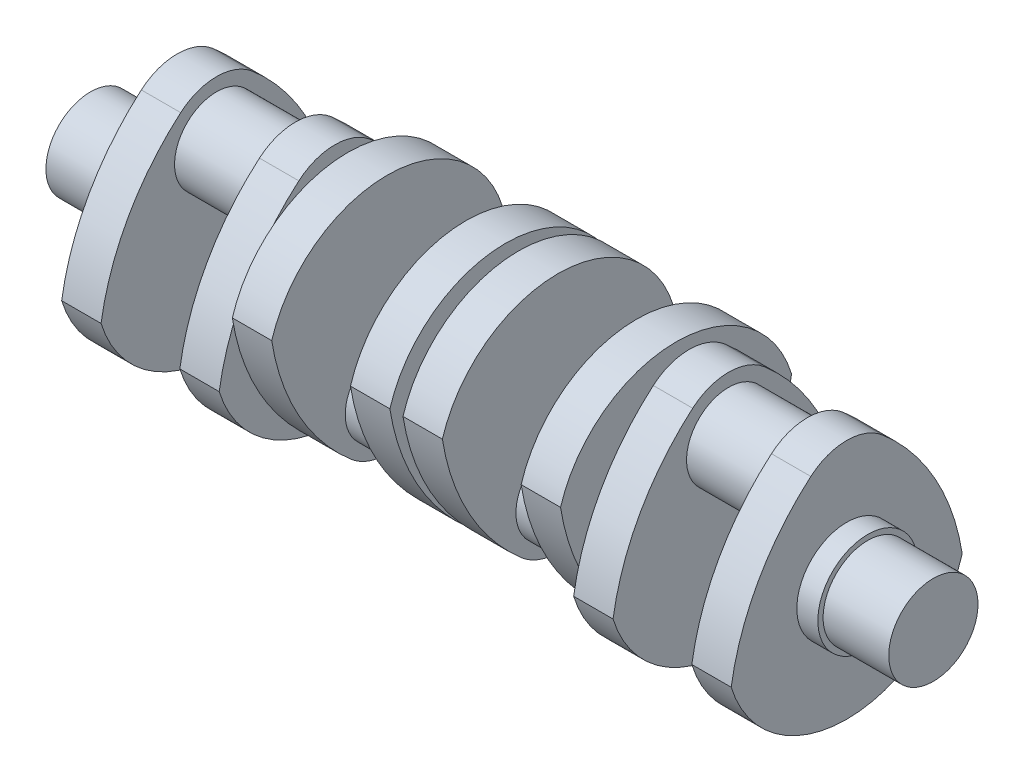
SolidWorks part; units mm, degrees
ref_plane "Front Plane" through (0, 0, 0) normal (0, 0, 1) x (1, 0, 0)
ref_plane "Top Plane" through (0, 0, 0) normal (0, 1, 0) x (1, 0, 0)
ref_plane "Right Plane" through (0, 0, 0) normal (1, 0, 0) x (0, 0, -1)
sketch "Sketch2" plane through (0, 0, 0) normal (1, 0, 0) x (0, 0, -1)
  circle A0 centre (0, 0) radius 17
  circle A1 centre (0, 0) radius 19
  dimension "D1" = 38
  dimension "D2" = 34
extrude "Boss-Extrude1" add sketch "Sketch2" against normal blind 25 contours A0
extrude "Boss-Extrude2" add sketch "Sketch2<4>" along normal blind 8 contours A1
sketch "Sketch2<4>" plane through (0, 0, 0) normal (1, 0, 0) x (0, 0, -1) same geometry as "Sketch2"
sketch "Sketch4" plane through (8, 0, 0) normal (1, 0, 0) x (0, 0, -1)
  arc A0 (-13.6681, 40.9431) -> (13.6681, 40.9431) centre (0, 25) cw
  arc A1 (-44, -13.4164) -> (44, -13.4164) centre (0, 0) ccw
  arc A2 (-13.6681, 40.9431) -> (-44, -13.4164) centre (44.9095, -27.3845) ccw
  arc A3 (13.6681, 40.9431) -> (44, -13.4164) centre (-44.9095, -27.3845) cw
  dimension "D3" = 46
  dimension "D4" = 21
  dimension "D5" = 90
  dimension "D6" = 90
  dimension "D1" = 25
  dimension "D2" = 88
extrude "Boss-Extrude3" add sketch "Sketch4" along normal blind 15
sketch "Sketch5" plane through (23, 0, 0) normal (1, 0, 0) x (0, 0, -1)
  circle A0 centre (0, 25) radius 16
  dimension "D1" = 32
extrude "Boss-Extrude4" add sketch "Sketch5" along normal blind 15
mirror "Mirror1" about plane through (38, 25, 0) normal (1, 0, 0) of "Boss-Extrude4", "Boss-Extrude3"
sketch "Sketch6" plane through (68, 0, 0) normal (1, 0, 0) x (0, 0, -1)
  circle A0 centre (0, 0) radius 17
  dimension "D1" = 34
extrude "Boss-Extrude5" add sketch "Sketch6" along normal blind 5
sketch "Sketch7" plane through (73, 0, 0) normal (1, 0, 0) x (0, 0, -1)
  arc A8 (-13.6681, -40.9431) -> (13.6681, -40.9431) centre (0, -25) ccw
  arc A9 (-44, 13.4164) -> (-13.6681, -40.9431) centre (44.9095, 27.3845) ccw
  arc A10 (44, 13.4164) -> (-44, 13.4164) centre (0, 0) ccw
  arc A11 (13.6681, -40.9431) -> (44, 13.4164) centre (-44.9095, 27.3845) ccw
extrude "Boss-Extrude6" add sketch "Sketch7" along normal blind 15
sketch "Sketch8" plane through (88, 0, 0) normal (1, 0, 0) x (0, 0, -1)
  circle A0 centre (0, -25) radius 16
  dimension "D1" = 32
  dimension "D2" = 25
extrude "Boss-Extrude7" add sketch "Sketch8" along normal blind 30
sketch "Sketch9" plane through (118, 0, 0) normal (1, 0, 0) x (0, 0, -1)
  arc A4 (-13.6681, -40.9431) -> (13.6681, -40.9431) centre (0, -25) ccw
  arc A5 (13.6681, -40.9431) -> (44, 13.4164) centre (-44.9095, 27.3845) ccw
  arc A6 (44, 13.4164) -> (-44, 13.4164) centre (0, 0) ccw
  arc A7 (-44, 13.4164) -> (-13.6681, -40.9431) centre (44.9095, 27.3845) ccw
  arc A8 (-13.6681, -40.9431) -> (13.6681, -40.9431) centre (0, -25) ccw
  arc A9 (13.6681, -40.9431) -> (44, 13.4164) centre (-44.9095, 27.3845) ccw
  arc A10 (44, 13.4164) -> (-44, 13.4164) centre (0, 0) ccw
  arc A11 (-44, 13.4164) -> (-13.6681, -40.9431) centre (44.9095, 27.3845) ccw
  dimension "D1" = 0
extrude "Boss-Extrude8" add sketch "Sketch9" along normal blind 15
sketch "Sketch10" plane through (133, 0, 0) normal (1, 0, 0) x (0, 0, -1)
  circle A0 centre (0, 0) radius 17
  dimension "D1" = 34
extrude "Boss-Extrude9" add sketch "Sketch10" along normal blind 2.5
mirror "Mirror2" about plane through (135.5, 0, 0) normal (1, 0, 0) of bodies 110
